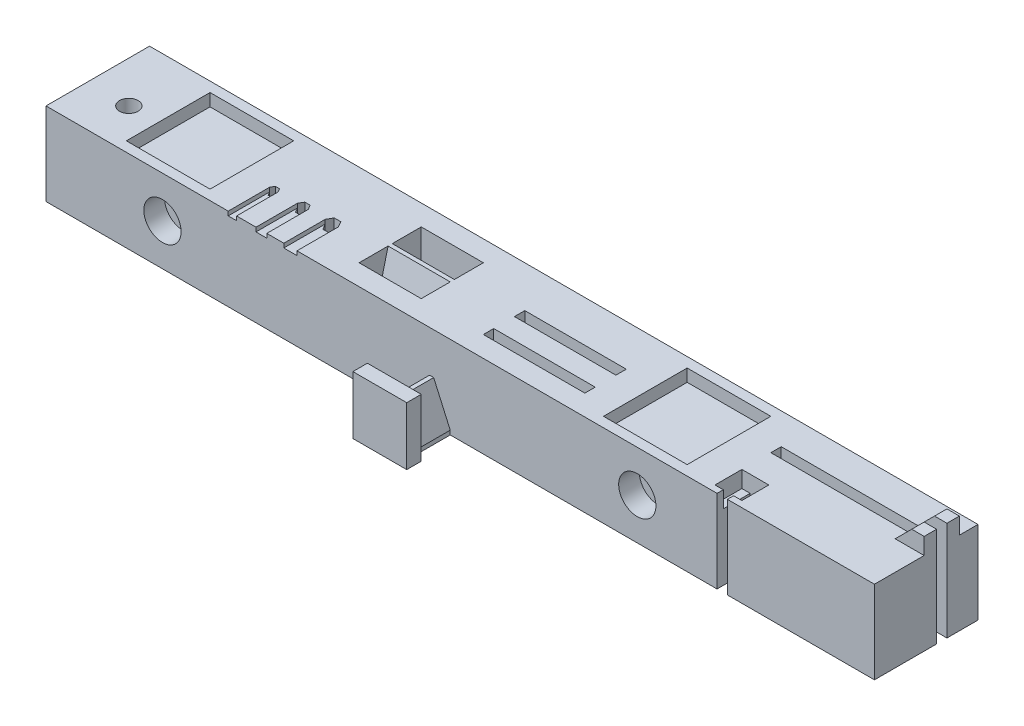
SolidWorks part; units mm, degrees
ref_plane "Piano frontale" through (0, 0, 0) normal (0, 0, 1) x (1, 0, 0)
ref_plane "Piano superiore" through (0, 0, 0) normal (0, 1, 0) x (1, 0, 0)
ref_plane "Piano destro" through (0, 0, 0) normal (1, 0, 0) x (0, 0, -1)
sketch "Schizzo1" plane through (0, 0, 0) normal (0, 0, 1) x (1, 0, 0)
  line L1 (-63.299, 14.3184) -> (136.701, 14.3184)
  line L2 (-63.299, 14.3184) -> (-63.299, -5.6816)
  line L3 (-63.299, -5.6816) -> (136.701, -5.6816)
  line L4 (136.701, 14.3184) -> (136.701, -5.6816)
  dimension "D1" = 20
  dimension "D2" = 200
extrude "Estrusione-Estrusione1" add sketch "Schizzo1" along normal blind 25
sketch "Schizzo2" plane through (0, 14.3184, 0) normal (0, 1, 0) x (1, 0, 0)
  line L0 (136.701, 0) -> (-63.299, 0) construction
  line L2 (-63.299, -25) -> (-63.299, 0) construction
  line L3 (-18.8041, -15.875) -> (-17.7938, -15.875)
  line L4 (-17.7938, -15.875) -> (-17.2886, -15)
  line L5 (-17.2886, -15) -> (-17.7938, -14.125)
  line L6 (-17.7938, -14.125) -> (-18.8041, -14.125)
  line L7 (-18.8041, -14.125) -> (-19.3093, -15)
  line L8 (-19.3093, -15) -> (-18.8041, -15.875)
  line L9 (-9.9999, -15) -> (-10.6494, -13.875)
  line L10 (-10.6494, -13.875) -> (-11.9485, -13.875)
  line L11 (-11.9485, -13.875) -> (-12.598, -15)
  line L12 (-12.598, -15) -> (-11.9485, -16.125)
  line L13 (-11.9485, -16.125) -> (-10.6494, -16.125)
  line L14 (-10.6494, -16.125) -> (-9.9999, -15)
  line L15 (-3.5051, -16.375) -> (-2.7113, -15)
  line L16 (-2.7113, -15) -> (-3.5051, -13.625)
  line L17 (-3.5051, -13.625) -> (-5.0928, -13.625)
  line L18 (-5.0928, -13.625) -> (-5.8867, -15)
  line L19 (-5.8867, -15) -> (-5.0928, -16.375)
  line L20 (-5.0928, -16.375) -> (-3.5051, -16.375)
  circle A0 centre (-53.299, -15) radius 2.25
  circle A1 centre (-18.299, -15) radius 0.875 construction
  circle A2 centre (-11.299, -15) radius 1.125 construction
  circle A3 centre (-4.299, -15) radius 1.375 construction
  dimension "D2" = 4.5
  dimension "D4" = 1.75
  dimension "D5" = 2.25
  dimension "D6" = 2.75
  dimension "D1" = 15
  dimension "D3" = 10
  dimension "D7" = 35
  dimension "D8" = 7
  dimension "D9" = 7
  dimension "D10" = 15
  dimension "D11" = 15
  dimension "D12" = 15
extrude "Taglio-Estrusione1" cut sketch "Schizzo2" against normal through all
sketch "Schizzo4" plane through (0, 14.3184, 0) normal (0, 1, 0) x (1, 0, 0)
  line L0 (136.701, -25) -> (-63.299, -25) construction
  line L1 (-19.3093, -15) -> (-17.2886, -15)
  line L2 (-19.3093, -15) -> (-19.3093, -25)
  line L3 (-19.3093, -25) -> (-17.2886, -25)
  line L4 (-17.2886, -15) -> (-17.2886, -25)
  line L5 (-12.598, -15) -> (-9.9999, -15)
  line L6 (-12.598, -15) -> (-12.598, -25)
  line L7 (-12.598, -25) -> (-9.9999, -25)
  line L8 (-9.9999, -15) -> (-9.9999, -25)
  line L10 (-5.8867, -15) -> (-2.7113, -15)
  line L11 (-5.8867, -15) -> (-5.8867, -25)
  line L12 (-5.8867, -25) -> (-2.7113, -25)
  line L13 (-2.7113, -15) -> (-2.7113, -25)
extrude "Taglio-Estrusione2" cut sketch "Schizzo4" against normal blind 1
sketch "Schizzo7" plane through (0, 14.3184, 0) normal (0, 1, 0) x (1, 0, 0)
  line L0 (136.701, -25) -> (-2.7113, -25) construction
  line L1 (7.2887, -14.5) -> (22.2887, -14.5)
  line L2 (7.2887, -14.5) -> (7.2887, -20)
  line L3 (7.2887, -20) -> (22.2887, -20)
  line L4 (22.2887, -14.5) -> (22.2887, -20)
  line L5 (7.2887, -5) -> (22.2887, -5)
  line L6 (7.2887, -5) -> (7.2887, -10.5)
  line L7 (7.2887, -10.5) -> (22.2887, -10.5)
  line L8 (22.2887, -5) -> (22.2887, -10.5)
  dimension "D1" = 15
  dimension "D2" = 15
  dimension "D3" = 15
  dimension "D4" = 4
  dimension "D5" = 5.5
  dimension "D6" = 5
  dimension "D7" = 10
extrude "Taglio-Estrusione3" cut sketch "Schizzo7" against normal through all
chamfer "Smusso1" distance 1.5 distance2 6 2 edges at (14.7887, 14.3184, 14.5) (14.7887, 14.3184, 10.5) first distance on face at (14.7887, 14.3184, 7.75)
sketch "Schizzo8" plane through (0, 14.3184, 0) normal (0, 1, 0) x (1, 0, 0)
  line L0 (7.2887, -20) -> (22.2887, -20) construction
  line L1 (37.2887, -17.5) -> (61.7887, -17.5)
  line L2 (37.2887, -17.5) -> (37.2887, -20)
  line L3 (37.2887, -20) -> (61.7887, -20)
  line L4 (61.7887, -17.5) -> (61.7887, -20)
  line L5 (37.2887, -10) -> (61.7887, -10)
  line L6 (37.2887, -10) -> (37.2887, -12.5)
  line L7 (37.2887, -12.5) -> (61.7887, -12.5)
  line L8 (61.7887, -10) -> (61.7887, -12.5)
  line L9 (22.2887, -12) -> (22.2887, -5) construction
  point P10 (22.2887, -8.5)
  dimension "D1" = 24.5
  dimension "D2" = 24.5
  dimension "D3" = 2.5
  dimension "D4" = 2.5
  dimension "D5" = 5
  dimension "D6" = 15
extrude "Taglio-Estrusione4" cut sketch "Schizzo8" against normal blind 13
sketch "Schizzo9" plane through (0, 14.3184, 0) normal (0, 1, 0) x (1, 0, 0)
  line L0 (136.701, -25) -> (136.701, 0) construction
  line L1 (96.701, -7.5) -> (136.701, -7.5)
  line L2 (96.701, -7.5) -> (96.701, -10)
  line L3 (96.701, -10) -> (136.701, -10)
  line L4 (136.701, -7.5) -> (136.701, -10)
  line L5 (136.701, 0) -> (-63.299, 0) construction
  dimension "D1" = 40
  dimension "D2" = 2.5
  dimension "D3" = 7.5
extrude "Taglio-Estrusione5" cut sketch "Schizzo9" against normal through all
sketch "Schizzo10" plane through (0, 14.3184, 0) normal (0, 1, 0) x (1, 0, 0)
  line L1 (136.701, -7.5) -> (129.701, -7.5)
  line L2 (136.701, -7.5) -> (136.701, -4.5)
  line L3 (136.701, -4.5) -> (129.701, -4.5)
  line L4 (129.701, -7.5) -> (129.701, -4.5)
  line L5 (136.701, -10) -> (129.701, -10)
  line L6 (136.701, -10) -> (136.701, -13)
  line L7 (136.701, -13) -> (129.701, -13)
  line L8 (129.701, -10) -> (129.701, -13)
  dimension "D1" = 7
  dimension "D2" = 7
  dimension "D3" = 3
  dimension "D4" = 3
extrude "Estrusione-Estrusione5" add sketch "Schizzo10" along normal blind 4
chamfer "Smusso2" distance 4 angle 45 2 edges at (129.701, 18.3184, 11.5) (129.701, 18.3184, 6)
sketch "Schizzo11" plane through (0, 14.3184, 0) normal (0, 1, 0) x (1, 0, 0)
  line L0 (136.701, -25) -> (-2.7113, -25) construction
  line L1 (98.701, -25) -> (101.201, -25)
  line L2 (98.701, -25) -> (98.701, -17)
  line L3 (98.701, -17) -> (101.201, -17)
  line L4 (101.201, -25) -> (101.201, -17)
  line L5 (96.701, -7.5) -> (96.701, -10) construction
  dimension "D1" = 2.5
  dimension "D2" = 8
  dimension "D3" = 2
extrude "Taglio-Estrusione6" cut sketch "Schizzo11" against normal through all
sketch "Schizzo12" plane through (0, 14.3184, 0) normal (0, 1, 0) x (1, 0, 0)
  line L0 (101.201, -17) -> (98.701, -17) construction
  line L1 (96.701, -17) -> (103.201, -17)
  line L2 (96.701, -17) -> (96.701, -23.5)
  line L3 (96.701, -23.5) -> (103.201, -23.5)
  line L4 (103.201, -17) -> (103.201, -23.5)
  line L7 (96.701, -7.5) -> (96.701, -10) construction
  dimension "D1" = 6.5
  dimension "D2" = 6.5
extrude "Taglio-Estrusione7" cut sketch "Schizzo12" against normal blind 4
sketch "Schizzo13" plane through (0, 0, 25) normal (0, 0, 1) x (1, 0, 0)
  line L0 (-63.299, -5.6816) -> (98.701, -5.6816) construction
  line L1 (25.2887, 4.3184) -> (34.2887, 4.3184)
  line L2 (25.2887, 4.3184) -> (25.2887, -5.6816)
  line L3 (25.2887, -5.6816) -> (34.2887, -5.6816)
  line L4 (34.2887, 4.3184) -> (34.2887, -5.6816)
  dimension "D1" = 10
  dimension "D2" = 3
  dimension "D3" = 9
extrude "Estrusione-Estrusione9" add sketch "Schizzo13" along normal blind 9 contours L2 L3 L4 L1
sketch "Schizzo14" plane through (0, 0, 34) normal (0, 0, 1) x (1, 0, 0)
  line L0 (25.2887, -5.6816) -> (34.2887, -5.6816) construction
  line L1 (23.2887, 8.3184) -> (36.2887, 8.3184)
  line L2 (23.2887, 8.3184) -> (23.2887, -5.6816)
  line L3 (23.2887, -5.6816) -> (36.2887, -5.6816)
  line L4 (36.2887, 8.3184) -> (36.2887, -5.6816)
  line L5 (25.2887, 4.3184) -> (25.2887, -5.6816) construction
  dimension "D1" = 13
  dimension "D2" = 14
  dimension "D3" = 2
extrude "Estrusione-Estrusione10" add sketch "Schizzo14" along normal blind 3.5
chamfer "Smusso3" distance 9 distance2 4 1 edges at (34.2887, 4.3184, 29.5) first distance on face at (34.2887, 0.5684, 30.625)
chamfer "Smusso4" distance 4 distance2 9 1 edges at (25.2887, 4.3184, 29.5) first distance on face at (27.7887, 4.3184, 29.5)
sketch "Schizzo16" plane through (0, 0, 25) normal (0, 0, 1) x (1, 0, 0)
  line L2 (-19.3093, 14.3184) -> (-63.299, 14.3184) construction
  line L3 (98.701, 14.3184) -> (-2.7113, 14.3184) construction
  circle A0 centre (-35.179, 4.3184) radius 2.25
  circle A1 centre (79.451, 4.3184) radius 2.25
  dimension "D3" = 4.5
  dimension "D4" = 4.5
  dimension "D1" = 17.25
  dimension "D2" = 15.87
  dimension "D5" = 10
  dimension "D6" = 10
extrude "Taglio-Estrusione8" cut sketch "Schizzo16" against normal through all
sketch "Schizzo17" plane through (0, 0, 25) normal (0, 0, 1) x (1, 0, 0)
  circle A0 centre (-35.179, 4.3184) radius 4.5
  circle A1 centre (79.451, 4.3184) radius 4.5
  dimension "D1" = 9
  dimension "D2" = 9
extrude "Taglio-Estrusione9" cut sketch "Schizzo17" against normal blind 5
sketch "Schizzo18" plane through (0, 14.3184, 0) normal (0, 1, 0) x (1, 0, 0)
  line L0 (136.701, 0) -> (-63.299, 0) construction
  line L1 (68.8887, -2.4) -> (89.0887, -2.4)
  line L2 (68.8887, -2.4) -> (68.8887, -22.6)
  line L3 (68.8887, -22.6) -> (89.0887, -22.6)
  line L4 (89.0887, -2.4) -> (89.0887, -22.6)
  line L5 (61.7887, -20) -> (61.7887, -17.5) construction
  line L10 (-46.299, -2.4) -> (-26.099, -2.4)
  line L11 (-46.299, -2.4) -> (-46.299, -22.6)
  line L12 (-46.299, -22.6) -> (-26.099, -22.6)
  line L13 (-26.099, -2.4) -> (-26.099, -22.6)
  circle A0 centre (-53.299, -15) radius 2.25 construction
  dimension "D8" = 7
  dimension "D1" = 20.2
  dimension "D2" = 20.2
  dimension "D3" = 2.4
  dimension "D4" = 7.1
  dimension "D5" = 20.2
  dimension "D6" = 20.2
  dimension "D7" = 2.4
extrude "Taglio-Estrusione10" cut sketch "Schizzo18" against normal blind 3
